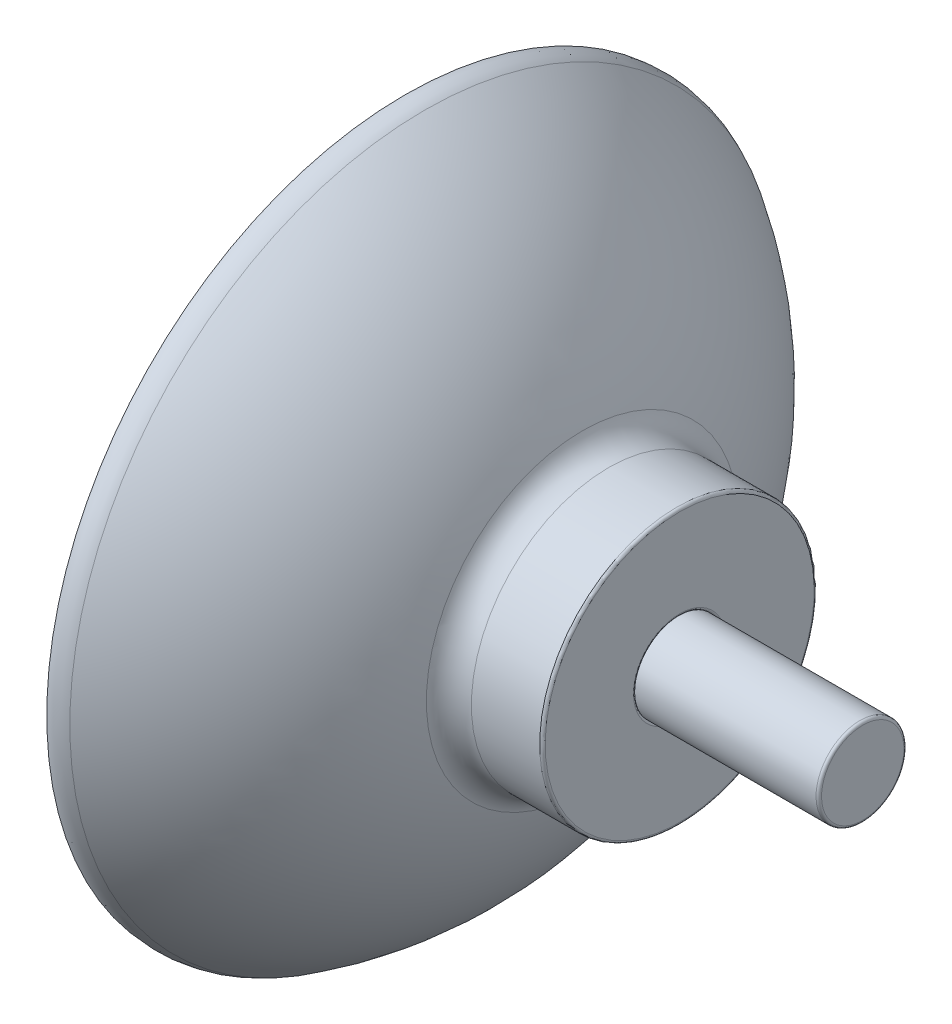
SolidWorks part; units mm, degrees
material "Rubber"
ref_plane "Front Plane" through (0, 0, 0) normal (0, 0, 1) x (1, 0, 0)
ref_plane "Top Plane" through (0, 0, 0) normal (0, 1, 0) x (1, 0, 0)
ref_plane "Right Plane" through (0, 0, 0) normal (1, 0, 0) x (0, 0, -1)
sketch "Sketch1" plane through (0, 0, 0) normal (0, 0, 1) x (1, 0, 0)
  line L0 (0, 0) -> (-10, 0) construction
  line L1 (0, 0) -> (5, 0) construction
  line L2 (0, 0) -> (0, 7.5)
  line L3 (0, 7.5) -> (5, 7.5)
  line L4 (5, 0) -> (5, 7.5)
  line L5 (2, 0) -> (4, 0) construction
  line L6 (2, 0) -> (2, 4.75)
  line L7 (2, 4.75) -> (4, 4.75)
  line L8 (4, 0) -> (4, 4.75)
  line L9 (-10, 0) -> (-10, 20) construction
  line L10 (-10, 20) -> (-10, 19.5)
  line L11 (0, 4) -> (0, 7.5)
  line L12 (4, 0) -> (5, 0)
  line L13 (2, 0) -> (0, 0)
  line L14 (4, 2.375) -> (5, 2.375)
  arc A0 (-10, 20) -> (0, 7.5) centre (-19.3122, 2.3002) cw
  arc A1 (-10, 19.5) -> (0, 4) centre (-21.7836, 0.9219) cw
  dimension "D8" = 20
  dimension "D11" = 22
  dimension "D1" = 5
  dimension "D2" = 7.5
  dimension "D3" = 2
  dimension "D4" = 1
  dimension "D5" = 4.75
  dimension "D6" = 20
  dimension "D7" = 10
  dimension "D9" = 0.5
  dimension "D10" = 3.5
revolve "Revolve1" add sketch "Sketch1" angle 360 about L0 region at (0.0901, 2, 0) region at (-3.1385, 12.951, 0)
fillet "Fillet1" radius 0.15 5 edges at (4, 2.375, 0) (5, 2.375, 0) (5, 7.5, 0) (-10, 19.5, 0) (0, 4, 0)
fillet "Fillet2" radius 1.5 2 edges at (-10, 20, 0) (0, 7.5, 0)
sketch "Sketch2" plane through (0, 0, 0) normal (0, 0, 1) x (1, 0, 0)
  line L0 (2, 0) -> (2, 4.75)
  line L1 (2, -4.75) -> (2, 4.75) construction
  line L2 (2, 4.75) -> (4, 4.75)
  line L3 (4, 4.75) -> (4, -4.75) construction
  line L4 (4, 4.75) -> (4, 2.4)
  line L5 (4, 2.4) -> (15, 2.4)
  line L6 (15, 2.4) -> (15, 0)
  line L7 (15, 0) -> (2, 0)
  line L8 (5, -7.35) -> (5, 7.35) construction
  dimension "D1" = 10
  dimension "D2" = 2.35
revolve "Revolve2" add sketch "Sketch2" angle 360 about L7
fillet "Fillet3" radius 0.15 1 edges at (15, 2.4, 0)
